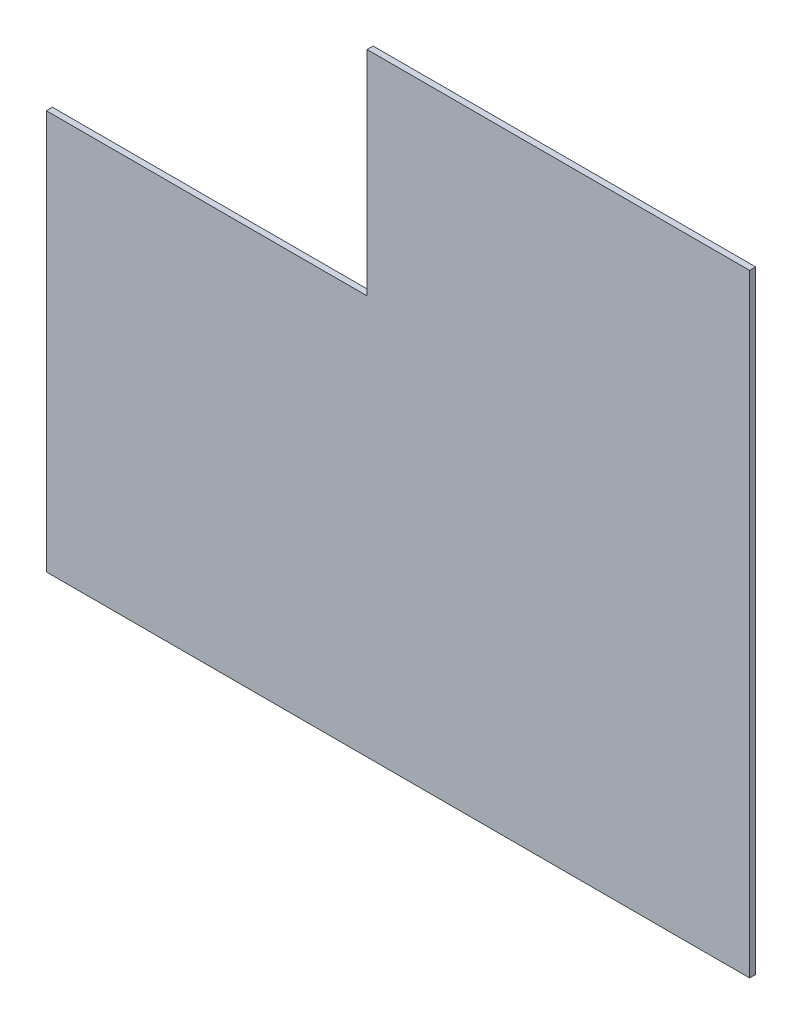
SolidWorks part; units mm, degrees
ref_plane "Спереди" through (0, 0, 0) normal (0, 0, 1) x (1, 0, 0)
ref_plane "Сверху" through (0, 0, 0) normal (0, 1, 0) x (1, 0, 0)
ref_plane "Справа" through (0, 0, 0) normal (1, 0, 0) x (0, 0, -1)
other "Configuration Table"
sketch "Эскиз2" plane through (0, 0, 0) normal (0, 0, 1) x (1, 0, 0)
  line L0 (507, 153.715) -> (0, 153.715) construction
  line L1 (1162.3, -506.285) -> (0, -506.285)
  line L2 (1162.3, -506.285) -> (1162.3, 506.285)
  line L3 (1162.3, 506.285) -> (540, 506.285)
  line L6 (0, -506.285) -> (0, 153.715)
  line L7 (0, 153.715) -> (530, 153.715)
  line L9 (540, 456.285) -> (540, -506.285) construction
  line L11 (530, 153.715) -> (530, 506.285)
  line L12 (530, 506.285) -> (540, 506.285)
  point P9 (0, 0)
  dimension "D1" = 10
extrude "Бобышка-Вытянуть1" add sketch "Эскиз2" against normal blind 10
equation "\"Ширина груза\"= 420"
equation "\"Глубина груза\"= 490"
equation "\"Высота груза\"= 297"
equation "\"Ширина ячейки\"= \"Ширина груза\" + 10"
equation "\"Глубина ячейки\"= \"Глубина груза\" + 10"
equation "\"Высота ячейки\"= \"Высота груза\" + 10 + 13"
equation "\"Колво ячеек ширина\"= 2"
equation "\"Колво ячеек высота\"= 2"
equation "\"Толщина стенки\"= 10"
equation "\"Крепление дверцы\"= 5"
equation "\"Ширина рейки\"= \"Толщина шестерни\""
equation "\"Высота рейки\"= 20"
equation "\"Высота пола\"= 20"
equation "\"Колво полозьев\"= 5"
equation "\"Отступ рейки\"= 20"
equation "\"Глубина каретки\"= \"Глубина ячейки\" + 30 + \"Мотор Y высота корпуса\" + 20"
equation "\"Длинна рейки\"= ( \"Ширина ячейки\" + \"Толщина стенки\" + \"Крепление дверцы\" ) * \"Колво ячеек ширина\" + \"Ширина ячейки выгрузки\" * \"Колво выгрузки\" + \"Толщина стенки\""
equation "\"Отступ шпильки\"= 26"
equation "\"Диаметр шпильки\"= 5"
equation "\"Длинна шпильки\"= ( \"Высота ячейки\" + \"Толщина стенки\" + \"Высота пола\" ) * \"Колво ячеек высота\" + ( \"Толщина стенки\" + \"Отступ рейки\" ) * 2 "
equation "\"Ширина пластины\"= 50  "
equation "\"Высота зона выгрузки\"= \"Высота ячейки\" * 2 + \"Толщина стенки\" * 2"
equation "\"Колво выгрузки\"= 1"
equation "\"Ширина ячейки выгрузки\"= \"Ширина ячейки\" + \"Толщина стенки\" + \"Отступ крепления мотора фиксации\"*2"
equation "\"Отступ крепления мотора фиксации\" = 30"
equation "\"Мотор X ширина корпуса\"= 42.3"
equation "\"Мотор X высота корпуса\"= 42.3"
equation "\"Мотор X длина корпуса\"= 40"
equation "\"Мотор X вылет вала\"= 19.8"
equation "\"Мотор Y ширина корпуса\"= 42.3"
equation "\"Мотор Y высота корпуса\"= 42.3"
equation "\"Мотор Y длина корпуса\"= 48"
equation "\"Мотор Y вылет вала\"= 30"
equation "\"Мотор Z ширина корпуса\"= 42"
equation "\"Мотор Z высота корпуса\"= 42"
equation "\"Мотор Z длина корпуса\"= 40"
equation "\"Мотор Z вылет вала\"= 23"
equation "\"Мотор диаметр вала ПРЕДВ\"= 5"
equation "\"Мотор шаг крепления ПРЕДВ\"= 31"
equation "\"Мотор диаметр отверстий ПРЕДВ\"= 3"
equation "\"Мотор глубина отверстий ПРЕДВ\"= 4.5"
equation "\"Мотор диаметр буртика ПРЕДВ\"= 22"
equation "\"Мотор высота буртика ПРЕДВ\"= 2"
equation "\"Мотор диаметр шкива ПРЕДВ\"= 16"
equation "\"Мотор длина шкива ПРЕДВ\"= 12"
equation "\"Мотор отступ шкива ПРЕДВ\"= 5"
equation "\"Мотор X шаг градусов\"= 1.8"
equation "\"Мотор Y шаг градусов\"= 1.8"
equation "\"Мотор Z шаг градусов\"= 1.8"
equation "\"Мотор Y диаметр ротора\"= 25.78"
equation "\"Толщина шестерни\"= 10"
equation "\"D1@Эскиз2\"=\"Толщина стенки\""
equation "\"D1@Бобышка-Вытянуть1\"=\"Толщина стенки\""
